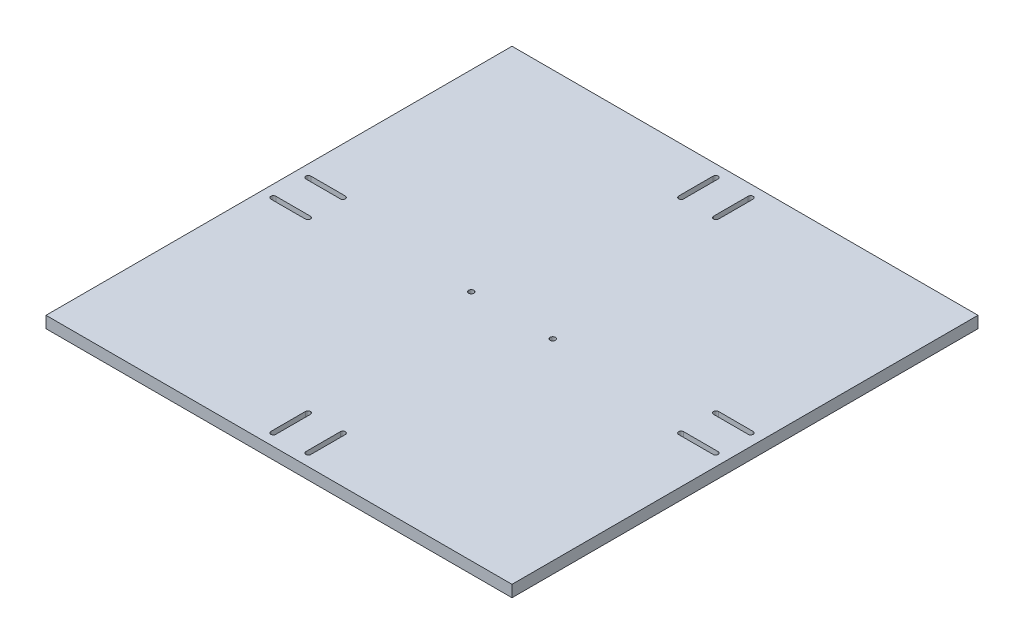
SolidWorks part; units mm, degrees
ref_plane "Plano frontal" through (0, 0, 0) normal (0, 0, 1) x (1, 0, 0)
ref_plane "Plano superior" through (0, 0, 0) normal (0, 1, 0) x (1, 0, 0)
ref_plane "Plano direito" through (0, 0, 0) normal (1, 0, 0) x (0, 0, -1)
sketch "Esboço1" plane through (0, 0, 0) normal (0, 1, 0) x (1, 0, 0)
  line L1 (0, 0) -> (400, 0)
  line L2 (0, 0) -> (0, 400)
  line L3 (0, 400) -> (400, 400)
  line L4 (400, 0) -> (400, 400)
  dimension "D1" = 400
extrude "Ressalto-extrusão1" add sketch "Esboço1" along normal blind 10
sketch "Esboço2" plane through (0, 10, 0) normal (0, 1, 0) x (1, 0, 0)
  line L0 (400, 400) -> (0, 400) construction
  line L1 (182.85, 389.85) -> (182.85, 360.15)
  line L2 (187.15, 389.85) -> (187.15, 360.15)
  line L3 (212.85, 389.85) -> (212.85, 360.15)
  line L4 (217.15, 389.85) -> (217.15, 360.15)
  line L5 (0, 200) -> (400, 200) construction
  line L6 (0, 400) -> (0, 0) construction
  line L7 (400, 0) -> (400, 400) construction
  line L8 (200, 400) -> (200, 0) construction
  line L9 (0, 0) -> (400, 0) construction
  line L26 (389.85, 182.85) -> (360.15, 182.85)
  line L27 (389.85, 187.15) -> (360.15, 187.15)
  line L28 (389.85, 212.85) -> (360.15, 212.85)
  line L41 (389.85, 217.15) -> (360.15, 217.15)
  line L42 (182.85, 10.15) -> (182.85, 39.85)
  line L43 (187.15, 10.15) -> (187.15, 39.85)
  line L44 (212.85, 10.15) -> (212.85, 39.85)
  line L45 (217.15, 10.15) -> (217.15, 39.85)
  line L46 (10.15, 217.15) -> (39.85, 217.15)
  line L47 (10.15, 212.85) -> (39.85, 212.85)
  line L48 (10.15, 187.15) -> (39.85, 187.15)
  line L49 (10.15, 182.85) -> (39.85, 182.85)
  arc A0 (187.15, 389.85) -> (182.85, 389.85) centre (185, 389.85) ccw
  arc A1 (182.85, 360.15) -> (187.15, 360.15) centre (185, 360.15) ccw
  arc A2 (217.15, 389.85) -> (212.85, 389.85) centre (215, 389.85) ccw
  arc A3 (212.85, 360.15) -> (217.15, 360.15) centre (215, 360.15) ccw
  arc A32 (389.85, 182.85) -> (389.85, 187.15) centre (389.85, 185) ccw
  arc A33 (360.15, 187.15) -> (360.15, 182.85) centre (360.15, 185) ccw
  arc A34 (360.15, 217.15) -> (360.15, 212.85) centre (360.15, 215) ccw
  arc A35 (389.85, 212.85) -> (389.85, 217.15) centre (389.85, 215) ccw
  arc A36 (182.85, 10.15) -> (187.15, 10.15) centre (185, 10.15) ccw
  arc A37 (187.15, 39.85) -> (182.85, 39.85) centre (185, 39.85) ccw
  arc A38 (217.15, 39.85) -> (212.85, 39.85) centre (215, 39.85) ccw
  arc A39 (212.85, 10.15) -> (217.15, 10.15) centre (215, 10.15) ccw
  arc A40 (10.15, 217.15) -> (10.15, 212.85) centre (10.15, 215) ccw
  arc A41 (39.85, 212.85) -> (39.85, 217.15) centre (39.85, 215) ccw
  arc A42 (39.85, 182.85) -> (39.85, 187.15) centre (39.85, 185) ccw
  arc A43 (10.15, 187.15) -> (10.15, 182.85) centre (10.15, 185) ccw
  point P17 (200, 400)
  point P64 (200, 200)
  dimension "D1" = 4.3
  dimension "D3" = 4.3
  dimension "D2" = 10.15
  dimension "D4" = 29.7
  dimension "D5" = 30
  dimension "D6" = 15
  dimension "D7" = 4
extrude "Corte-extrusão2" cut sketch "Esboço2" against normal through all both
sketch "Esboço3" plane through (0, 10, 0) normal (0, 1, 0) x (1, 0, 0)
  line L0 (0, 200) -> (400, 200) construction
  line L1 (0, 400) -> (0, 0) construction
  line L2 (400, 0) -> (400, 400) construction
  line L3 (200, 400) -> (200, 0) construction
  line L4 (400, 400) -> (0, 400) construction
  line L5 (0, 0) -> (400, 0) construction
  circle A0 centre (165, 200) radius 2.25
  circle A1 centre (235, 200) radius 2.25
  point P16 (0, 0)
  point P17 (0, 0)
  dimension "D2" = 4.5
  dimension "D3" = 4.5
  dimension "D1" = 70
  dimension "D4" = 35
extrude "Corte-extrusão3" cut sketch "Esboço3" against normal through all
